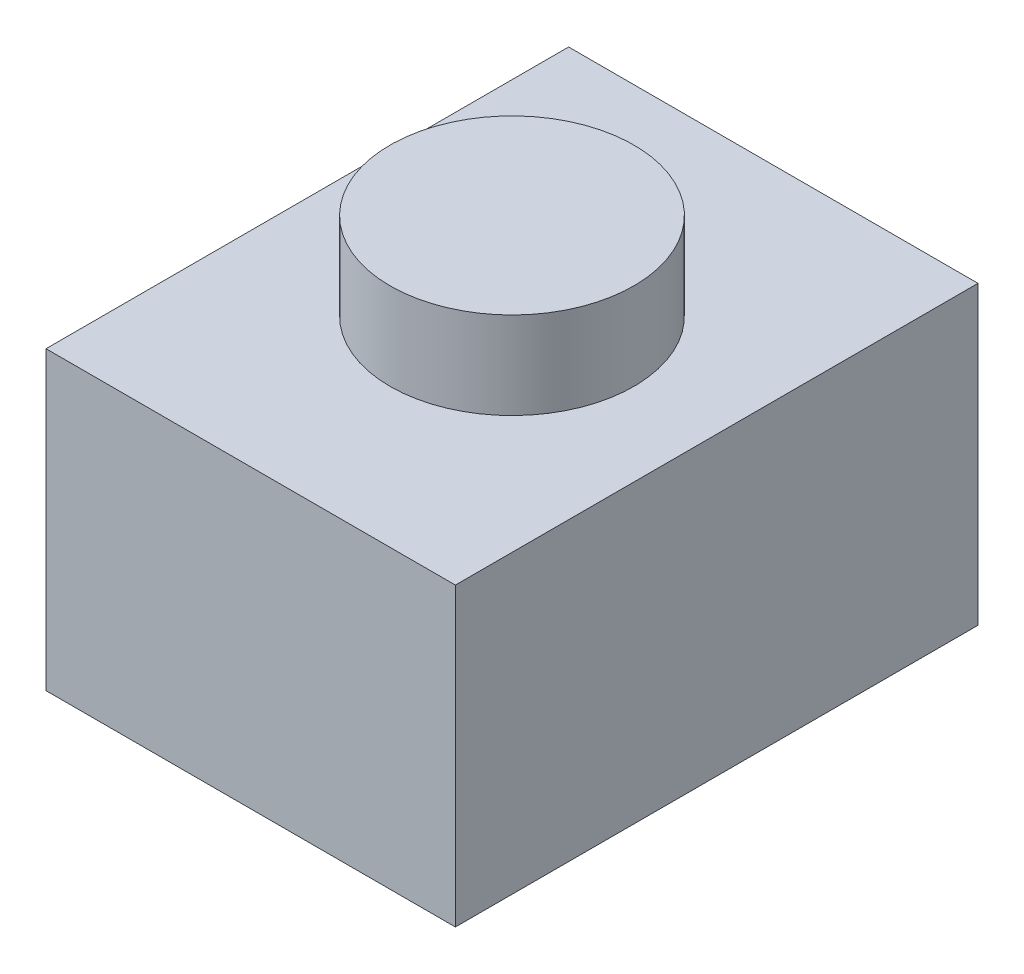
SolidWorks part; units mm, degrees
ref_plane "Front Plane" through (0, 0, 0) normal (0, 0, 1) x (1, 0, 0)
ref_plane "Top Plane" through (0, 0, 0) normal (0, 1, 0) x (1, 0, 0)
ref_plane "Right Plane" through (0, 0, 0) normal (1, 0, 0) x (0, 0, -1)
sketch "Sketch1" plane through (0, 0, 0) normal (0, 1, 0) x (1, 0, 0)
  line L1 (-2.9845, -3.81) -> (2.9845, -3.81)
  line L2 (-2.9845, -3.81) -> (-2.9845, 3.81)
  line L3 (-2.9845, 3.81) -> (2.9845, 3.81)
  line L4 (2.9845, -3.81) -> (2.9845, 3.81)
  line L5 (-2.9845, -3.81) -> (2.9845, 3.81) construction
  line L6 (-2.9845, 3.81) -> (2.9845, -3.81) construction
  point P0 (0, 0)
  dimension "D1" = 5.969
  dimension "D2" = 7.62
extrude "Boss-Extrude1" add sketch "Sketch1" along normal blind 4.318
sketch "Sketch2" plane through (0, 4.318, 0) normal (0, 1, 0) x (1, 0, 0)
  circle A0 centre (0, 0) radius 1.778
  dimension "D1" = 3.556
extrude "Boss-Extrude2" add sketch "Sketch2" along normal blind 1.27
